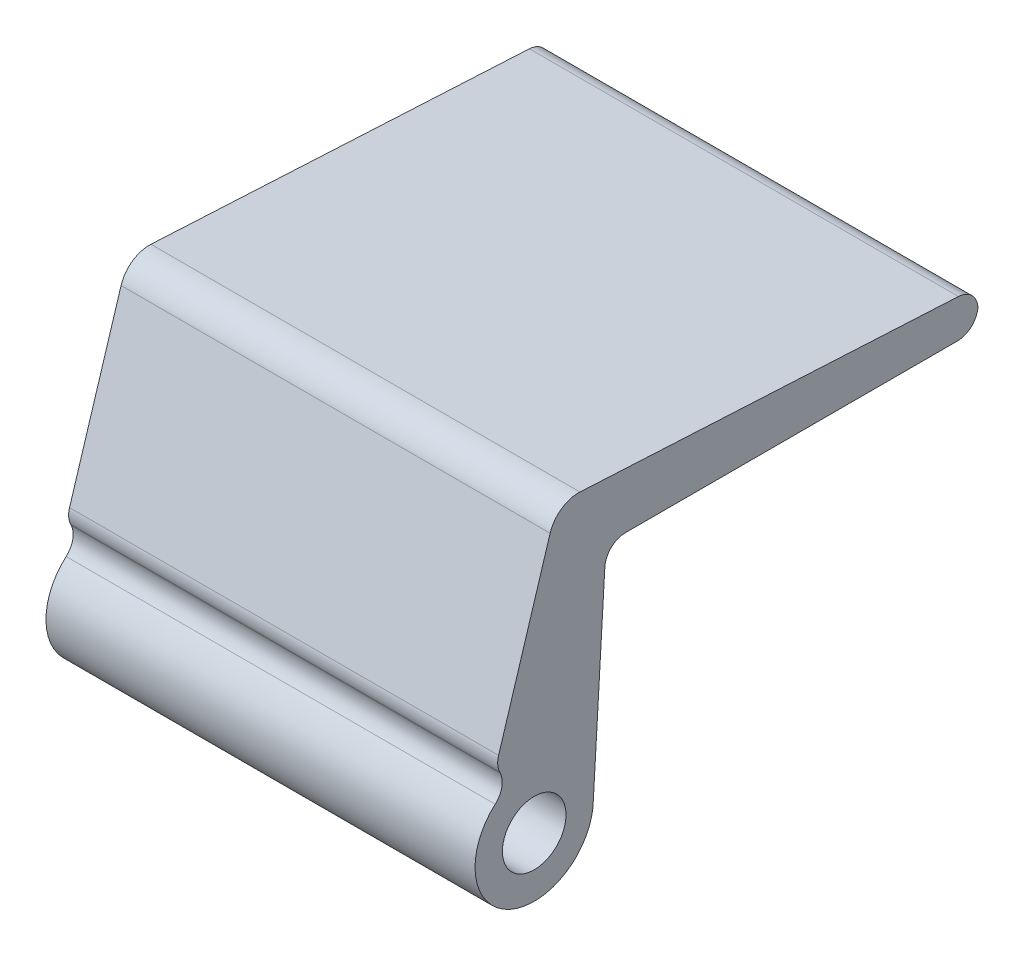
SolidWorks part; units mm, degrees
ref_plane "Front Plane" through (0, 0, 0) normal (0, 0, 1) x (1, 0, 0)
ref_plane "Top Plane" through (0, 0, 0) normal (0, 1, 0) x (1, 0, 0)
ref_plane "Right Plane" through (0, 0, 0) normal (1, 0, 0) x (0, 0, -1)
sketch "Sketch1" plane through (0, 0, 0) normal (1, 0, 0) x (0, 0, -1)
  line L30 (1.536, 18.5) -> (-2.5722, 5.2199)
  line L34 (-2.5722, 5.2199) -> (-1.7681, 3.588)
  line L35 (4.8214, 14) -> (4, 0)
  line L42 (30, 17) -> (1.536, 18.5)
  line L43 (30, 17) -> (30, 14.5)
  line L44 (4.8214, 14) -> (4.8214, 14.5)
  line L45 (26.5205, 14.5) -> (4.8214, 14.5)
  line L47 (26.5205, 14.5) -> (30, 14.5)
  circle A5 centre (0, 0) radius 2.15
  arc A8 (-1.7681, 3.588) -> (4, 0) centre (0, 0) ccw
extrude "Boss-Extrude1" add sketch "Sketch1" along normal mid plane 29
fillet "Fillet1" radius 2 1 edges at (0, 18.5, -1.536)
fillet "Fillet2" radius 1.4 5 edges at (0, 3.588, 1.7681) (0, 5.2199, 2.5722) (0, 17, -30) (0, 14.5, -30) (0, 14.5, -4.8214)
